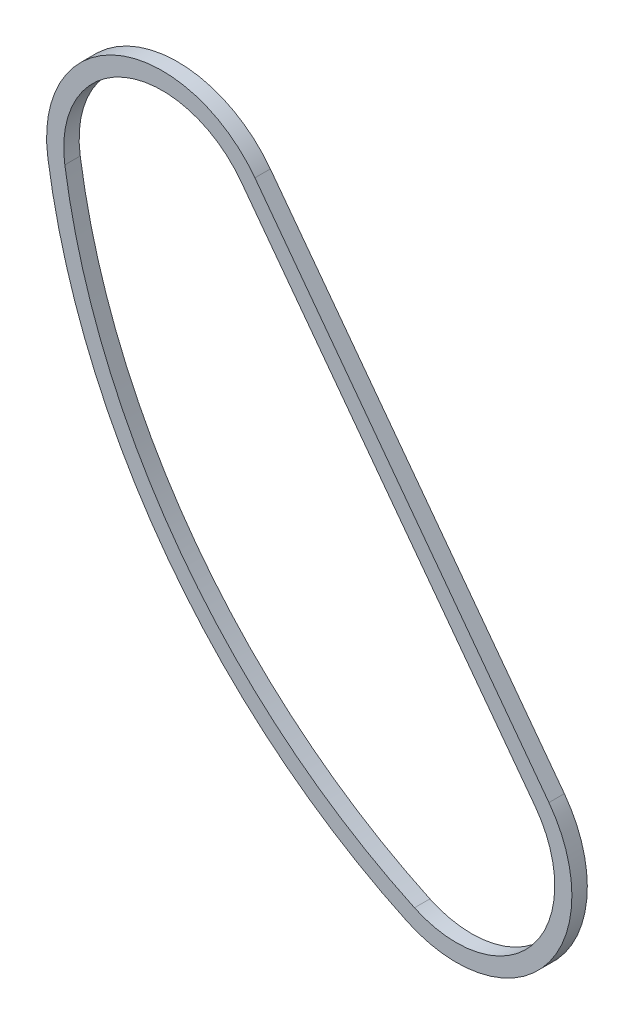
SolidWorks part; units mm, degrees
material "Plain Carbon Steel"
ref_plane "Front Plane" through (0, 0, 0) normal (0, 0, 1) x (1, 0, 0)
ref_plane "Top Plane" through (0, 0, 0) normal (0, 1, 0) x (1, 0, 0)
ref_plane "Right Plane" through (0, 0, 0) normal (1, 0, 0) x (0, 0, -1)
sketch "Sketch1" plane through (0, 0, 0) normal (0, 0, 1) x (1, 0, 0)
  line L0 (112.8547, -94.7973) -> (27.0486, 20.1851)
  line L1 (108.8475, -97.7877) -> (23.0414, 17.1947)
  arc A0 (27.0486, 20.1851) -> (-33.374, -5.0237) centre (0, 0) ccw
  arc A1 (-33.374, -5.0237) -> (71.4917, -145.5464) centre (150.2493, 22.6164) ccw
  arc A2 (71.4917, -145.5464) -> (112.8547, -94.7973) centre (85.8061, -114.9824) ccw
  arc A3 (23.0414, 17.1947) -> (-28.4297, -4.2794) centre (0, 0) ccw
  arc A4 (-28.4297, -4.2794) -> (73.6124, -141.0184) centre (150.2493, 22.6164) ccw
  arc A5 (73.6124, -141.0184) -> (108.8475, -97.7877) centre (85.8061, -114.9824) ccw
extrude "Boss-Extrude1" add sketch "Sketch1" along normal blind 4.5
